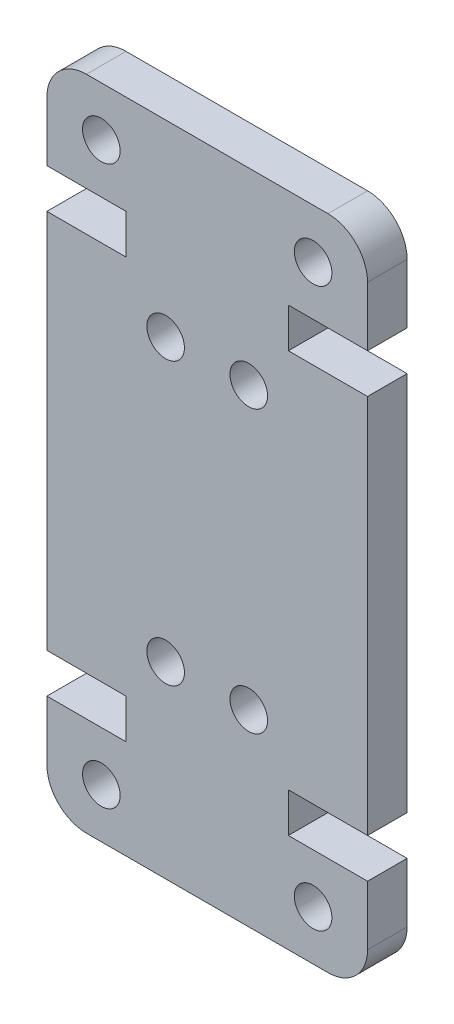
SolidWorks part; units mm, degrees
ref_plane "Front Plane" through (0, 0, 0) normal (0, 0, 1) x (1, 0, 0)
ref_plane "Top Plane" through (0, 0, 0) normal (0, 1, 0) x (1, 0, 0)
ref_plane "Right Plane" through (0, 0, 0) normal (1, 0, 0) x (0, 0, -1)
sketch "Sketch1" plane through (0, 0, 0) normal (0, 0, 1) x (1, 0, 0)
  line L0 (0, 26.21) -> (0, 7)
  line L1 (16.2, 2) -> (16.2, 5)
  line L2 (12.2, 5) -> (16.2, 5)
  line L3 (2, 0) -> (14.2, 0)
  line L4 (16.2, 7) -> (12.2, 7)
  line L5 (12.2, 7) -> (12.2, 5)
  line L6 (16.2, 26.21) -> (16.2, 7)
  line L7 (4, 7) -> (4, 5)
  line L8 (0, 31.21) -> (0, 28.21)
  line L9 (4, 28.21) -> (0, 28.21)
  line L10 (0, 7) -> (4, 7)
  line L11 (0, 26.21) -> (4, 26.21)
  line L12 (4, 5) -> (0, 5)
  line L13 (4, 26.21) -> (4, 28.21)
  line L14 (12.2, 26.21) -> (12.2, 28.21)
  line L15 (16.2, 26.21) -> (12.2, 26.21)
  line L16 (0, 2) -> (0, 5)
  line L17 (2, 33.21) -> (14.2, 33.21)
  line L18 (12.2, 28.21) -> (16.2, 28.21)
  line L19 (16.2, 31.21) -> (16.2, 28.21)
  line L20 (0, 16.605) -> (16.2, 16.605) construction
  line L21 (8.1, 33.21) -> (8.1, 0) construction
  circle A0 centre (13.45, 2.5) radius 0.95
  circle A1 centre (10.2, 9.5) radius 0.95
  arc A2 (16.2, 2) -> (14.2, 0) centre (14.2, 2) cw
  circle A3 centre (2.75, 30.71) radius 0.95
  circle A4 centre (6, 23.71) radius 0.95
  arc A5 (0, 2) -> (2, 0) centre (2, 2) ccw
  arc A6 (0, 31.21) -> (2, 33.21) centre (2, 31.21) cw
  circle A7 centre (6, 9.5) radius 0.95
  arc A8 (16.2, 31.21) -> (14.2, 33.21) centre (14.2, 31.21) ccw
  circle A9 centre (2.75, 2.5) radius 0.95
  circle A10 centre (10.2, 23.71) radius 0.95
  circle A11 centre (13.45, 30.71) radius 0.95
  point P15 (8.1, 16.605)
  dimension "D1" = 1.9
  dimension "D2" = 2
  dimension "D3" = 2.75
  dimension "D4" = 6
  dimension "D5" = 8.1
  dimension "D6" = 2.5
  dimension "D9" = 9.5
  dimension "D10" = 16.605
  dimension "D7" = 5
extrude "Boss-Extrude1" add sketch "Sketch1" along normal blind 4
sketch "Sketch2" plane through (0, 0, 0) normal (0, 0, 1) x (1, 0, 0)
  line L0 (0, 0) -> (16.2, 0)
  line L1 (16.2, 0) -> (16.2, 33.21)
  line L2 (16.2, 33.21) -> (0, 33.21)
  line L3 (0, 33.21) -> (0, 0)
extrude "Cut-Extrude2" cut sketch "Sketch2" along normal blind 2
equation "\"D5@Sketch1\"= \"fingerWidth@parametersSketch@prostheticParameters.SLDPRT\" / 2'PIP width"
equation "\"D10@Sketch1\"= ( \"HL@parametersSketch@prostheticParameters.SLDPRT\" * 0.266 - 12 - 4 ) / 2 'PIP length - Sil. sht PIP-Sil Sht MIP"
equation "\"D1@Sketch1\"= 1.5 + \"tol1@parametersSketch@prostheticParameters.SLDPRT\""
